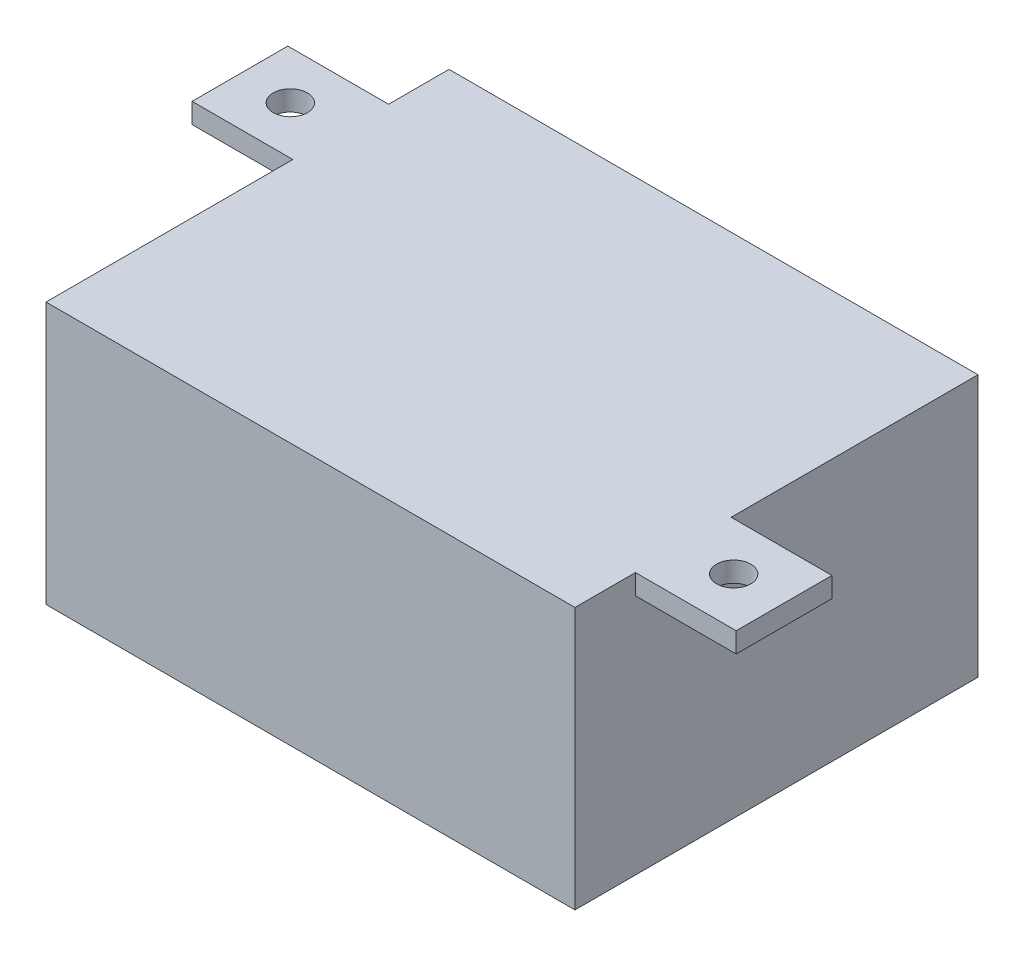
SolidWorks part; units mm, degrees
ref_plane "Front Plane" through (0, 0, 0) normal (0, 0, 1) x (1, 0, 0)
ref_plane "Top Plane" through (0, 0, 0) normal (0, 1, 0) x (1, 0, 0)
ref_plane "Right Plane" through (0, 0, 0) normal (1, 0, 0) x (0, 0, -1)
sketch "Case Sketch" plane through (0, 0, 0) normal (0, 1, 0) x (1, 0, 0)
  line L0 (-26.25, 20) -> (26.25, 20)
  line L1 (26.25, 20) -> (26.25, -20)
  line L2 (26.25, -20) -> (-26.25, -20)
  line L3 (-26.25, -20) -> (-26.25, 20)
extrude "Case" add sketch "Case Sketch" along normal blind 26 from offset 66.57
ref_axis "Engine Axis" through (39.875, 0, 0) along (-1, 0, 0)
sketch "Ears Sketch" plane through (0, 0, 0) normal (0, 1, 0) x (1, 0, 0)
  line L0 (26.25, -4.5) -> (36.25, -4.5)
  line L1 (36.25, -4.5) -> (36.25, -14)
  line L2 (36.25, -14) -> (26.25, -14)
  line L3 (26.25, -14) -> (26.25, -4.5)
  line L4 (-36.25, 14) -> (-26.25, 14)
  line L5 (-26.25, 14) -> (-26.25, 4.5)
  line L6 (-26.25, 4.5) -> (-36.25, 4.5)
  line L7 (-36.25, 4.5) -> (-36.25, 14)
  circle A0 centre (-31.25, 9.25) radius 1.7
  circle A1 centre (31.25, -9.25) radius 1.7
extrude "Ears" add sketch "Ears Sketch" along normal blind 2 from offset 90.57
